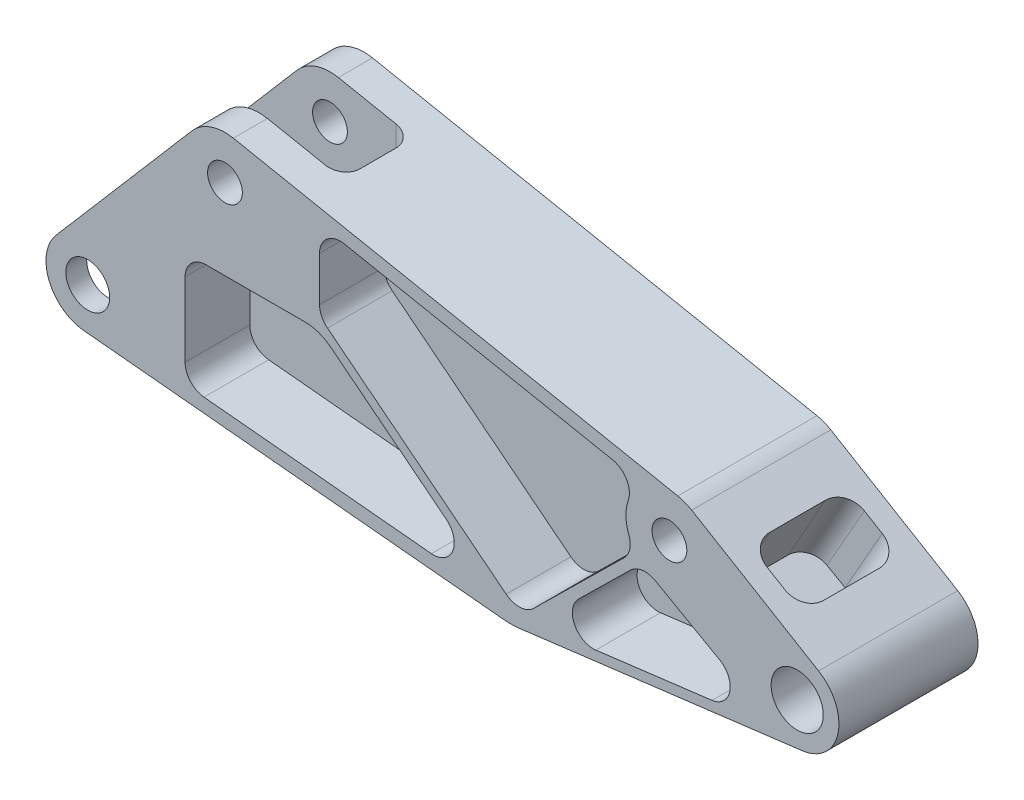
SolidWorks part; units mm, degrees
material "6061-T6 (SS)"
ref_plane "Front Plane" through (0, 0, 0) normal (1, 0, 0) x (0, 1, 0)
ref_plane "Top Plane" through (0, 0, 0) normal (0, 0, 1) x (0, 1, 0)
ref_plane "Right Plane" through (0, 0, 0) normal (0, 1, 0) x (-1, 0, 0)
sketch "Sketch1" plane through (0, 0, 0) normal (0, 0, 1) x (0, 1, 0)
  line L1 (21.356, 21.793) -> (37.358, 102.9455)
  line L2 (5.8317, 135.319) -> (34.7405, 110.5039)
  line L3 (6.5414, -3.9083) -> (20.3824, 19.2574)
  line L5 (14.8385, 114.2971) -> (14.8385, 127.5877)
  line L6 (16.8705, 89.241) -> (16.8705, 125.8434)
  line L9 (-2.4791, 111.7571) -> (11.0285, 111.7571)
  line L10 (16.8705, 89.241) -> (34.6557, 89.241)
  line L12 (4.2983, 19.4547) -> (-1.3308, 9.5091)
  line L14 (14.8385, 107.9471) -> (14.8385, 89.9006)
  line L15 (-13.1015, 50.4298) -> (20.0455, 92.416) construction
  line L16 (-6.2716, 108.311) -> (-10.2563, 66.785)
  line L17 (-14.2126, 52.1469) -> (-6.7167, 130.2649)
  line L20 (13.1993, 85.1789) -> (-3.4733, 64.0603)
  line L21 (15.9233, 85.7599) -> (-9.8354, 53.1323)
  line L23 (30.7695, 82.662) -> (21.1158, 33.7042)
  line L25 (18.9137, 87.209) -> (27.0315, 87.209)
  line L26 (4.2983, 19.4547) -> (16.4059, 12.6019)
  line L27 (-1.3308, 9.5091) -> (10.5427, 2.7888)
  line L28 (-13.1015, 50.4298) -> (13.5685, 23.3286) construction
  line L29 (-10.4937, 36.7653) -> (-7.8375, 15.5634)
  line L30 (-9.5606, 48.0991) -> (6.6502, 31.6262)
  line L31 (-0.7413, 14.1604) -> (5.9072, 25.9071)
  line L32 (14.8385, 114.2971) -> (-8.2489, 114.2971)
  line L33 (5.3071, 30.4561) -> (-3.9976, 39.9113)
  line L34 (-7.5609, -0.9472) -> (-14.2126, 52.1469)
  circle A0 centre (0, 0) radius 4.7625
  circle A1 centre (29.5705, 104.481) radius 3.175
  circle A2 centre (0.8685, 129.5371) radius 4
  circle A3 centre (13.5685, 23.3286) radius 3.175
  arc A4 (-7.5609, -0.9472) -> (6.5414, -3.9083) centre (0, 0) ccw
  arc A5 (-6.7167, 130.2649) -> (5.8317, 135.319) centre (0.8685, 129.5371) cw
  arc A6 (37.358, 102.9455) -> (34.7405, 110.5039) centre (29.5705, 104.481) ccw
  arc A7 (20.3824, 19.2574) -> (21.356, 21.793) centre (13.5685, 23.3286) ccw
  arc A17 (21.1158, 33.7042) -> (16.1423, 30.8372) centre (17.3778, 34.4413) cw
  arc A23 (14.8385, 89.9006) -> (13.1993, 85.1789) centre (7.2185, 89.9006) cw
  arc A24 (-10.2563, 66.785) -> (-3.4733, 64.0603) centre (-6.4637, 66.4211) ccw
  arc A25 (27.0315, 87.209) -> (30.7695, 82.662) centre (27.0315, 83.399) cw
  arc A26 (18.9137, 87.209) -> (15.9233, 85.7599) centre (18.9137, 83.399) ccw
  arc A28 (-2.4791, 111.7571) -> (-6.2716, 108.311) centre (-2.4791, 107.9471) ccw
  arc A29 (-9.8354, 53.1323) -> (-9.5606, 48.0991) centre (-6.845, 50.7714) ccw
  arc A30 (-10.4937, 36.7653) -> (-3.9976, 39.9113) centre (-6.7132, 37.2389) cw
  arc A32 (6.6502, 31.6262) -> (10.7288, 30.7407) centre (9.3658, 34.2986) ccw
  arc A33 (-7.8375, 15.5634) -> (-0.7413, 14.1604) centre (-4.057, 16.037) ccw
  arc A34 (11.0285, 111.7571) -> (14.8385, 107.9471) centre (11.0285, 107.9471) cw
  circle A35 centre (20.0455, 92.416) radius 3.175 construction
  arc A36 (10.7288, 30.7407) -> (16.1423, 30.8372) centre (13.5685, 23.3286) cw
  arc A37 (5.3071, 30.4561) -> (5.9072, 25.9071) centre (2.5915, 27.7837) cw
  dimension "D1" = 38.1
  dimension "D4" = 6.35
  dimension "D5" = 9.525
  dimension "D6" = 8
  dimension "D7" = 26.9875
  dimension "D8" = 7.62
  dimension "D9" = 7.62
  dimension "D10" = 7.9375
  dimension "D11" = 7.9375
  dimension "D19" = 2.54
  dimension "D22" = 1.778
  dimension "D24" = 3.81
  dimension "D25" = 3.81
  dimension "D26" = 1.778
  dimension "D29" = 3.81
  dimension "D30" = 12.7
  dimension "D31" = 3.81
  dimension "D32" = 3.81
  dimension "D33" = 7.62
  dimension "D34" = 3.81
  dimension "D35" = 3.81
  dimension "D36" = 1.27
  dimension "D14" = 3.81
  dimension "D20" = 3.81
  dimension "D28" = 3.81
  dimension "D39" = 6.35
  dimension "D40" = 1.778
  dimension "D12" = 3.81
  dimension "D2" = 129.54
  dimension "D3" = 108.585
  dimension "D13" = 15.24
  dimension "D15" = 13.97
  dimension "D16" = 12.7
  dimension "D17" = 2.032
  dimension "D18" = 2.032
  dimension "D21" = 1.778
  dimension "D23" = 2.54
  dimension "D27" = 2.54
  dimension "D37" = 0.889
  dimension "D38" = 15.24
  dimension "D41" = 13.97
extrude "Boss-Extrude1" add sketch "Sketch1" along normal mid plane 25.4 contours L1 A6 L2 L6 L10 A1 | L3 A7 L1 L10 L6 L2 L5 A4 L27 L12 L26 A28 A23 L20 A24 L16 A17 A3 A0 L23 L21 A26 L25 A25 | A5 L5 L2 A2 | L12 L27 L3 L26 region at (-20.9986, 19.6363, 0) region at (-103.8939, 25.4238, 0) region at (-11.1047, 7.4884, 0) region at (-123.5763, 3.4351, 0)
extrude "Boss-Extrude2" add sketch "Sketch1<5>" along normal mid plane 1.778 contours L16 A24 L20 A23 | A17 | L23 A25 L25 A26 L21 | L29 A33 L31 L33 A30 region at (-90.503, 1.8814, 0) region at (-57.96, 12.4468, 0) region at (-26.9438, -3.1281, 0)
sketch "Sketch1<5>" plane through (0, 0, 0) normal (0, 0, 1) x (0, 1, 0) same geometry as "Sketch1"
extrude "Cut-Extrude1" cut sketch "Sketch1<6>" against normal mid plane 12.954 contours L1 A6 L2 L6 L10 A1 region at (-103.8939, 25.4238, 0)
sketch "Sketch1<6>" plane through (0, 0, 0) normal (0, 0, 1) x (0, 1, 0) same geometry as "Sketch1"
extrude "Cut-Extrude2" cut sketch "Sketch1<7>" against normal mid plane 17.78 contours A5 L5 L2 A2 region at (-123.5763, 3.4351, 0)
sketch "Sketch1<7>" plane through (0, 0, 0) normal (0, 0, 1) x (0, 1, 0) same geometry as "Sketch1"
extrude "Cut-Extrude3" cut sketch "Sketch1<9>" against normal mid plane 17.78 contours L12 L27 L3 L26 region at (-11.1047, 7.4884, 0)
sketch "Sketch1<9>" plane through (0, 0, 0) normal (0, 0, 1) x (0, 1, 0) same geometry as "Sketch1"
fillet "Fillet1" radius 3.81 8 edges at (-120.9424, 14.8385, 8.89) (-120.9424, 14.8385, -8.89) (-107.5422, 16.8705, 6.477) (-107.5422, 16.8705, -6.477) (-6.1489, 4.606, -8.89) (-16.0283, 10.3521, -8.89) (-16.0283, 10.3521, 8.89) (-6.1489, 4.606, 8.89)
fillet "Fillet2" radius 3.175 10 edges at (-89.241, 27.6681, -6.477) (-89.241, 17.9864, -5.3611) (-89.241, 27.6681, 6.477) (-89.241, 17.9864, 5.3611) (-89.241, 16.8705, 0) (-114.2971, 1.3898, -8.89) (-114.2971, 13.7226, -7.7741) (-114.2971, 1.3898, 8.89) (-114.2971, 13.7226, 7.7741) (-114.2971, 14.8385, 0)
sketch "Sketch2" plane through (0, 0, 0) normal (0, 0, 1) x (0, 1, 0)
  line L0 (0.8685, 129.5371) -> (-82.2041, 143.266)
  line L1 (29.5705, 104.481) -> (77.0079, 96.6413)
  line L2 (0.8685, 129.5371) -> (0, 0) construction
  dimension "D1" = 99
fillet "Fillet3" radius 12.7 1 edges at (-52.1469, -14.2126, 0)
